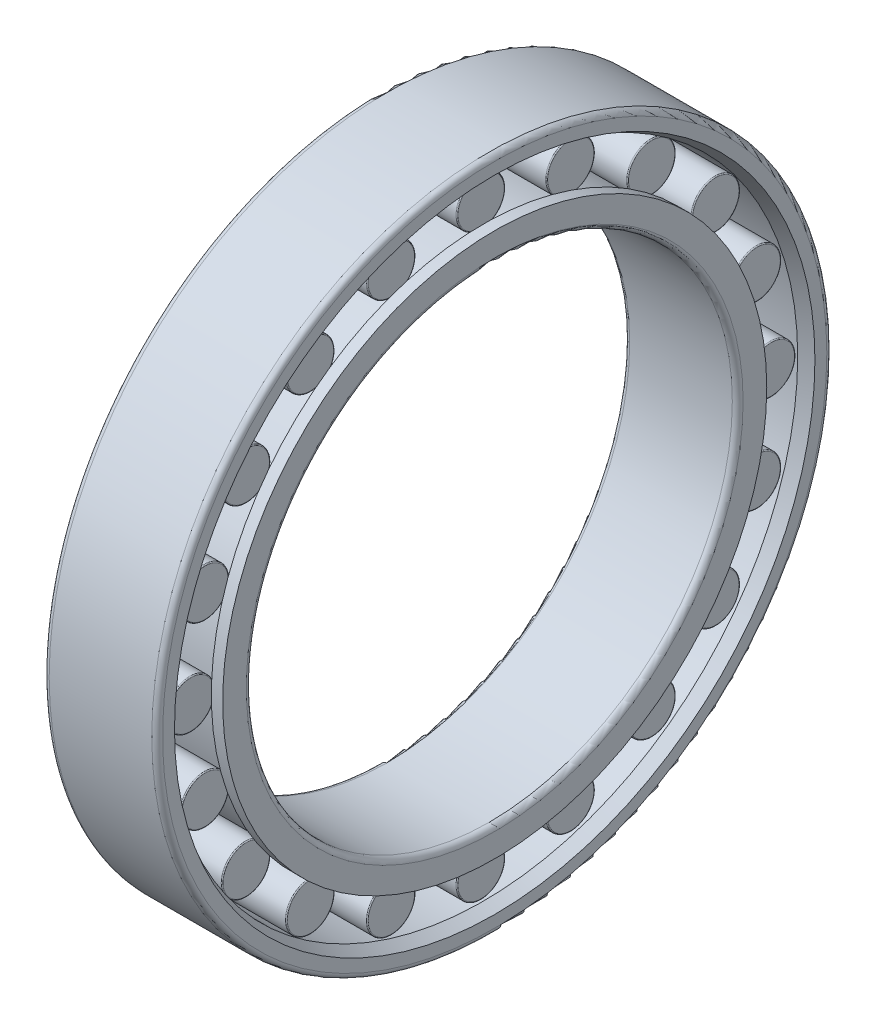
SolidWorks part; units mm, degrees
ref_plane "Plane1" through (0, 0, 0) normal (0, 0, 1) x (1, 0, 0)
ref_plane "Plane2" through (0, 0, 0) normal (0, 1, 0) x (1, 0, 0)
ref_plane "Plane3" through (0, 0, 0) normal (1, 0, 0) x (0, 0, -1)
sketch "Clipboard" plane through (0, 0, 0) normal (0, 0, 1) x (1, 0, 0)
  line L0 (-10, 0) -> (10, 0) construction
  line L1 (0, 0) -> (185.2698, -67.4327)
  line L2 (0, 0) -> (101.017, 36.7672)
  line L3 (0, 0) -> (218.798, -79.636)
  line L4 (0, 0) -> (-22.3471, -0.7804)
  dimension "Race_OD" = 232.84
  dimension "Race_ID" = 197.16
sketch "OutRacSke" plane through (0, 0, 0) normal (0, 0, 1) x (1, 0, 0)
  line L0 (16.8, 116.42) -> (21, 118.5944)
  line L1 (-21, 118.5944) -> (-21, 123)
  line L2 (-19, 125) -> (19, 125)
  line L3 (21, 123) -> (21, 118.5944)
  line L4 (-16.8, 116.42) -> (-21, 118.5944)
  line L6 (16.8, 116.42) -> (-16.8, 116.42)
  line L8 (-90, 0) -> (90, 0) construction
  arc A0 (-21, 123) -> (-19, 125) centre (-19, 123) cw
  arc A1 (19, 125) -> (21, 123) centre (19, 123) cw
  dimension "Race_OD" = 232.84
  dimension "groove_dp" = 2.1744
  dimension "halfCylLen" = 16.8
  dimension "radius" = 2
  dimension "halfWidth" = 21
  dimension "Cyl_Len" = 33.6
revolve "OuterRace" add sketch "OutRacSke" angle 360 about L8 reverse direction yes
sketch "RolDetSke" plane through (0, 0, 0) normal (0, 0, 1) x (1, 0, 0)
  line L0 (-15.96, 116.068) -> (-15.96, 107.5)
  line L1 (-15.96, 107.5) -> (15.96, 107.5)
  line L2 (15.96, 107.5) -> (15.96, 116.068)
  line L3 (15.603, 116.425) -> (-15.603, 116.425)
  line L4 (-33.6, 107.5) -> (33.6, 107.5) construction
  arc A0 (15.96, 116.068) -> (15.603, 116.425) centre (15.603, 116.068) ccw
  arc A1 (-15.603, 116.425) -> (-15.96, 116.068) centre (-15.603, 116.068) ccw
  dimension "radius" = 0.357
  dimension "Roller_diameter" = 17.85
  dimension "halfLength" = 15.96
revolve "RollerDetailed" add sketch "RolDetSke" angle 360 about L4 reverse direction yes
ref_axis "Axis1" through (-50, 0, 0) along (1, 0, 0)
sketch "RolSimSke" plane through (0, 101.6, 0) normal (0, 0, 1) x (1, 0, 0)
  line L0 (-15.96, 14.468) -> (-15.96, -2.668)
  line L1 (25.4, -101.6) -> (-25.4, -101.6) construction
  line L2 (15.96, -2.668) -> (15.96, 14.468)
  line L3 (15.603, 14.825) -> (-15.603, 14.825)
  line L5 (15.603, -3.025) -> (-15.603, -3.025)
  arc A0 (15.96, 14.468) -> (15.603, 14.825) centre (15.603, 14.468) ccw
  arc A1 (-15.603, 14.825) -> (-15.96, 14.468) centre (-15.603, 14.468) ccw
  arc A2 (15.96, -2.668) -> (15.603, -3.025) centre (15.603, -2.668) cw
  arc A3 (-15.603, -3.025) -> (-15.96, -2.668) centre (-15.603, -2.668) cw
  dimension "radius" = 0.357
  dimension "D1" = 98.575
  dimension "Roller_diameter" = 17.85
  dimension "halfLength" = 15.96
revolve "RollersSimplified" [suppressed] add sketch "RolSimSke" angle 360 about L1
sketch "InsRacSke" plane through (0, 0, 0) normal (0, 0, 1) x (1, 0, 0)
  line L0 (16.8, 98.58) -> (16.8, 100.7544)
  line L1 (-21, 100.7544) -> (-21, 92)
  line L2 (-19, 90) -> (19, 90)
  line L3 (21, 92) -> (21, 100.7544)
  line L4 (16.8, 100.7544) -> (21, 100.7544)
  line L5 (16.8, 98.58) -> (-16.8, 98.58)
  line L6 (-90, 0) -> (90, 0) construction
  line L8 (-16.8, 98.58) -> (-16.8, 100.7544)
  line L9 (-16.8, 100.7544) -> (-21, 100.7544)
  arc A0 (-21, 92) -> (-19, 90) centre (-19, 92) ccw
  arc A1 (19, 90) -> (21, 92) centre (19, 92) ccw
  dimension "halfCylLen" = 16.8
  dimension "radius" = 2
  dimension "Race_ID" = 197.16
  dimension "Width" = 42
  dimension "halfWidth" = 21
  dimension "Cyl_Len" = 33.6
  dimension "groove_dp" = 2.1744
revolve "InnerRace" add sketch "InsRacSke" angle 360 about L6 reverse direction yes
pattern_circular "RollersDetailed" count 20 every 18 about axis through (-50, 0, 0) along (1, 0, 0) of "RollerDetailed"
sketch "CagSpiSke" plane through (0, 0, 0) normal (0, 0, 1) x (1, 0, 0)
  line L0 (18.9, 105.2687) -> (18.9, 109.7313)
  line L1 (18.9, 109.7313) -> (-18.9, 109.7313)
  line L2 (-18.9, 109.7313) -> (-18.9, 105.2687)
  line L3 (-18.9, 105.2687) -> (18.9, 105.2687)
  line L4 (-90, 0) -> (90, 0) construction
revolve "CageSpine" [suppressed] add sketch "CagSpiSke" angle 360 about L4
equation "\"CLdia@Clipboard\" =  ( \"Race_OD@Clipboard\" + \"Race_ID@Clipboard\" )  / 4"
equation "\"Race_OD@OutRacSke\" = \"Race_OD@Clipboard\""
equation "\"halfCylLen@OutRacSke\" = \"Cyl_Len@OutRacSke\" / 2"
equation "\"RolCLRad@RolDetSke\" = \"CLdia@Clipboard\""
equation "\"Roller_diameter@RolDetSke\" =  ( \"Race_OD@Clipboard\" - \"Race_ID@Clipboard\" )  / 2 + .01"
equation "\"Roller_diameter@RolSimSke\" =  ( \"Race_OD@Clipboard\" - \"Race_ID@Clipboard\" )  / 2 + .01"
equation "\"radius@RolDetSke\" = \"Roller_diameter@RolDetSke\" / 50"
equation "\"Length@RolDetSke\" = \"Cyl_Len@OutRacSke\" * .95"
equation "\"halfLength@RolDetSke\" = \"Length@RolDetSke\" / 2"
equation "\"thickness@CagSpiSke\"  = \"Roller_diameter@RolDetSke\" * .25"
equation "\"Cag_IR@CagSpiSke\" =  \"RolCLRad@RolDetSke\" * 2 - \"thickness@CagSpiSke\""
equation "\"Rol_Length@RolSimSke\" = \"Cyl_Len@InsRacSke\" * .95"
equation "\"halfLength@RolSimSke\" = \"Rol_Length@RolSimSke\" / 2"
equation "\"radius@RolSimSke\" = \"radius@RolDetSke\""
equation "\"D1@RolSimSke\" = \"CLdia@Clipboard\" -  ( \"Roller_diameter@RolSimSke\" / 2 ) "
equation "\"Max_count@Clipboard\" = int( 3.14159265 / atn(( \"Roller_diameter@RolDetSke\" / 2) / sqr( \"RolCLRad@RolDetSke\"  *  \"RolCLRad@RolDetSke\" - ( \"Roller_diameter@RolDetSke\" / 2) *  ( \"Roller_diameter@RolDetSke\" / 2))))"
equation "\"Max_count@Clipboard\" = ((sgn( \"Max_count@Clipboard\" - \"Count@Clipboard\" )-1)*( \"Max_count@Clipboard\" - \"Count@Clipboard\" ))/-2+ \"Count@Clipboard\""
equation "\"Count@RollersDetailed\" = int( \"Show_count@Clipboard\" ) "
equation "\"Count@RollersDetailed\" = ((sgn( \"Count@RollersDetailed\" - \"Max_count@Clipboard\" )-1)*( \"Count@RollersDetailed\" - \"Max_count@Clipboard\" ))/-2+ \"Max_count@Clipboard\""
equation "\"Count@RollersDetailed\" = ((sgn( \"Count@RollersDetailed\" - \"Min_count@Clipboard\" )+1)*( \"Count@RollersDetailed\" - \"Min_count@Clipboard\"))/2 +\"Min_count@Clipboard\""
equation "\"Angle@RollersDetailed\" = 360.0 / \"Max_count@Clipboard\""
equation "\"radius@InsRacSke\" = \"radius@OutRacSke\""
equation "\"groove_dp@InsRacSke\" = \"groove_dp@OutRacSke\""
equation "\"Width@InsRacSke\" = \"Width@OutRacSke\""
equation "\"halfWidth@OutRacSke\" = \"Width@OutRacSke\" / 2"
equation "\"halfWidth@InsRacSke\" = \"Width@InsRacSke\" / 2"
equation "\"Race_ID@InsRacSke\" = \"Race_ID@Clipboard\""
equation "\"Cyl_Len@InsRacSke\" = \"Cyl_Len@OutRacSke\""
equation "\"halfCylLen@InsRacSke\" = \"Cyl_Len@InsRacSke\" / 2"
equation "\"Angle@CageSpine\" =  \"Angle@RollersDetailed\" * ( \"Count@RollersDetailed\" -1 + int( \"Count@RollersDetailed\" / \"Max_count@Clipboard\" ) )  + 0.001 -  int( \"Count@RollersDetailed\" / \"Max_count@Clipboard\" ) * 0.001"
equation "\"Angle@CageSpine\" =  \"Angle@CageSpine\" * int( \"Min_count@Clipboard\" / 2) + int(1 / \"Min_count@Clipboard\")  * 0.001"
equation "\"width@CagSpiSke\" =   ( \"Width@InsRacSke\" + \"Cyl_Len@InsRacSke\" )  / 2"
equation "\"halfwidth@CagSpiSke\" = \"width@CagSpiSke\" / 2"
